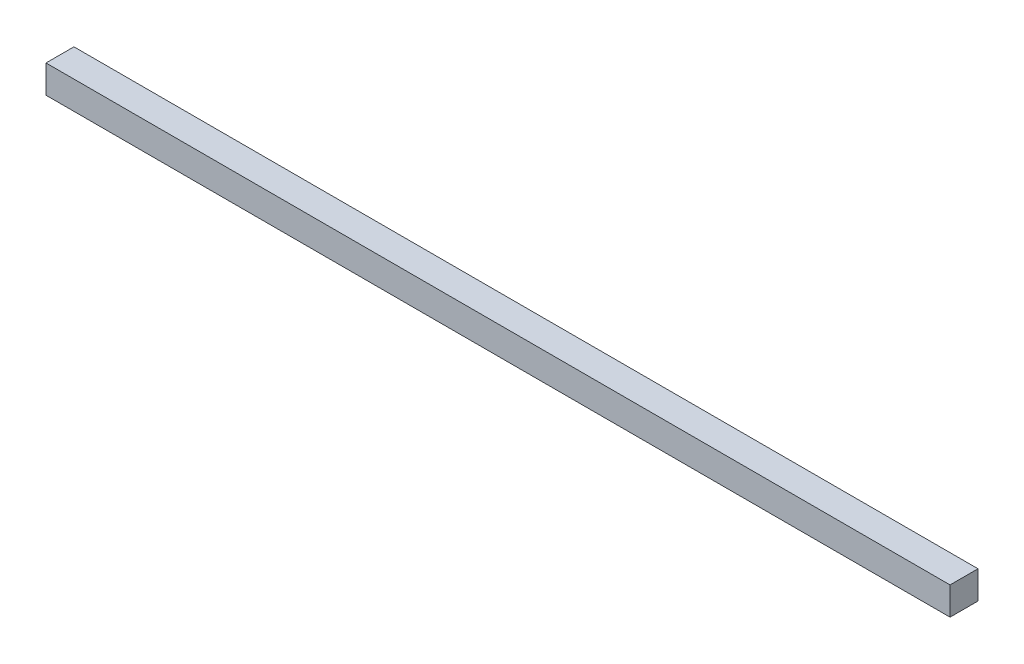
SolidWorks part; units mm, degrees
ref_plane "Front Plane" through (0, 0, 0) normal (0, 0, 1) x (1, 0, 0)
ref_plane "Top Plane" through (0, 0, 0) normal (0, 1, 0) x (1, 0, 0)
ref_plane "Right Plane" through (0, 0, 0) normal (1, 0, 0) x (0, 0, -1)
sketch "Sketch1" plane through (0, 0, 0) normal (1, 0, 0) x (0, 0, -1)
  line L1 (0, 0) -> (9.525, 0)
  line L2 (0, 0) -> (0, 9.525)
  line L3 (0, 9.525) -> (9.525, 9.525)
  line L4 (9.525, 0) -> (9.525, 9.525)
  dimension "D1" = 9.525
extrude "Boss-Extrude1" add sketch "Sketch1" against normal blind 307.975 contours L1 L4 L3 L2 region at (0, 4.7625, -4.7625)
